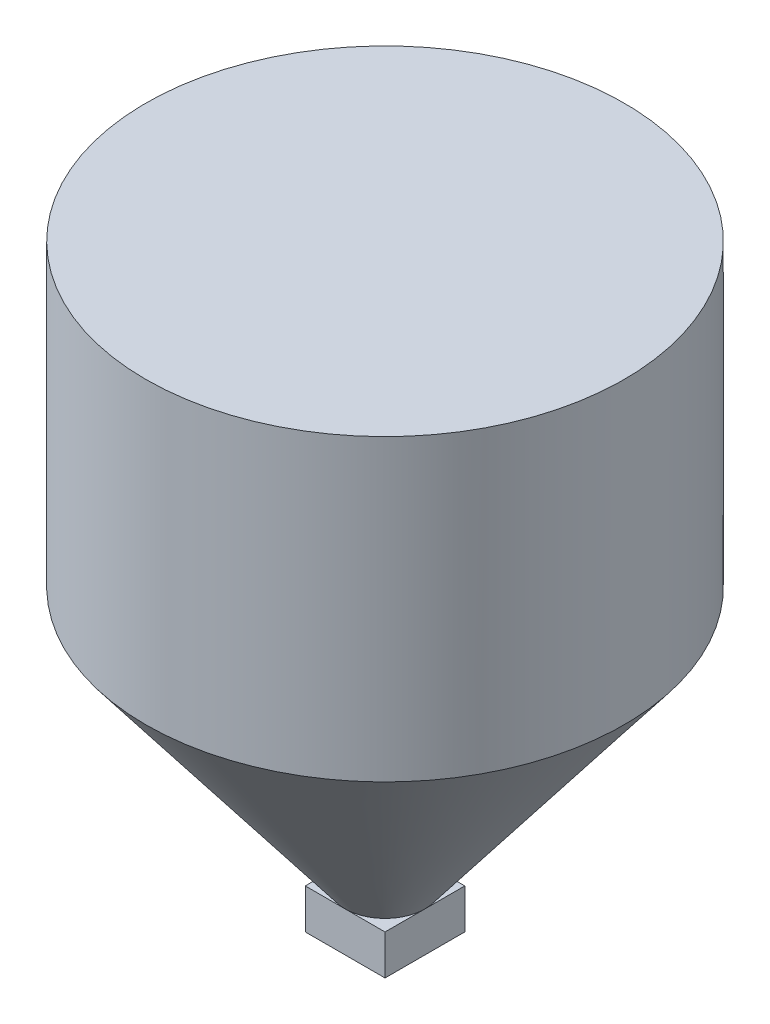
SolidWorks part; units mm, degrees
ref_plane "Alzado" through (0, 0, 0) normal (0, 0, 1) x (1, 0, 0)
ref_plane "Planta" through (0, 0, 0) normal (0, 1, 0) x (1, 0, 0)
ref_plane "Vista lateral" through (0, 0, 0) normal (1, 0, 0) x (0, 0, -1)
sketch "Croquis1" plane through (0, 0, 0) normal (0, 1, 0) x (1, 0, 0)
  circle A0 centre (0, 0) radius 300
  dimension "D1" = 600
ref_plane "Plano1" through (0, -700, 0) normal (0, 1, 0) x (1, 0, 0)
extrude "Saliente-Extruir1" add sketch "Croquis1" against normal blind 375 contours A0
sketch "Croquis2" plane through (0, -375, 0) normal (0, -1, 0) x (1, 0, 0)
  circle A0 centre (0, 0) radius 300
sketch "Croquis3" plane through (0, -700, 0) normal (0, 1, 0) x (1, 0, 0)
  circle A0 centre (0, 0) radius 50
  dimension "D1" = 100
loft "Recubrir1" add profiles "Croquis3", "Croquis2" connector at (-49.9253, -700, 2.7318) connector at (-299.408, -375, 18.8372)
sketch "Croquis5" plane through (0, -700, 0) normal (0, -1, 0) x (1, 0, 0)
  line L1 (50, 50) -> (-50, 50)
  line L2 (50, 50) -> (50, -50)
  line L3 (50, -50) -> (-50, -50)
  line L4 (-50, 50) -> (-50, -50)
  line L5 (50, 50) -> (-50, -50) construction
  line L6 (50, -50) -> (-50, 50) construction
  point P0 (0, 0)
  dimension "D1" = 100
  dimension "D2" = 100
extrude "Saliente-Extruir2" add sketch "Croquis5" along normal blind 50
